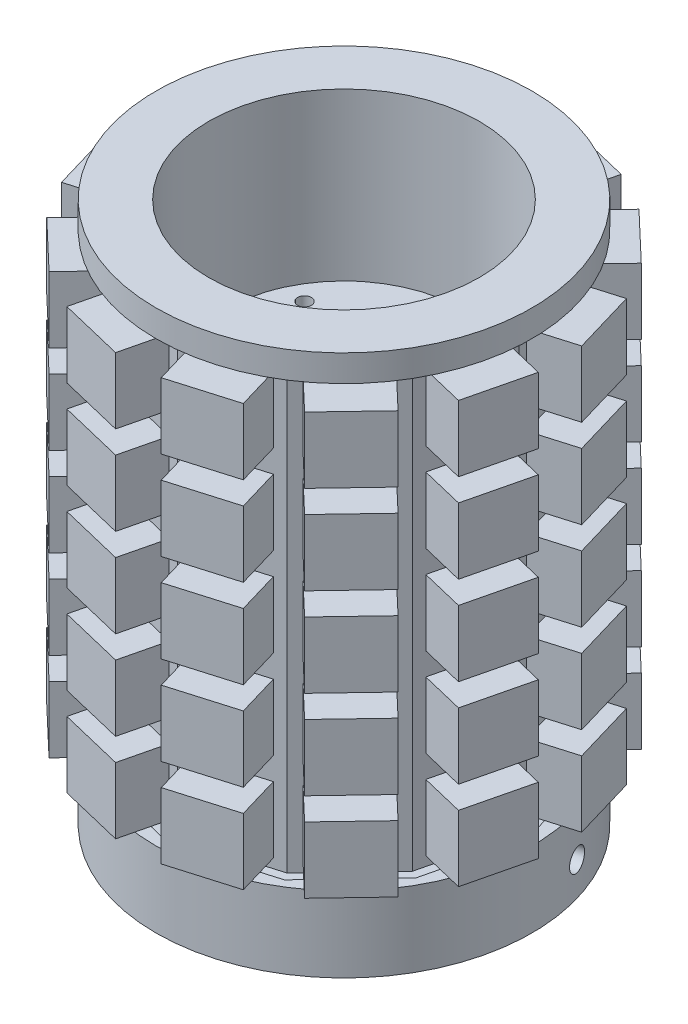
SolidWorks part; units mm, degrees
ref_plane "Front Plane" through (0, 0, 0) normal (0, 0, 1) x (1, 0, 0)
ref_plane "Top Plane" through (0, 0, 0) normal (0, 1, 0) x (1, 0, 0)
ref_plane "Right Plane" through (0, 0, 0) normal (1, 0, 0) x (0, 0, -1)
sketch "Sketch1" plane through (0, 0, 0) normal (0, 1, 0) x (1, 0, 0)
  circle A0 centre (0, 0) radius 36
ref_plane "Plane1" through (0, 70, 0) normal (0, 1, 0) x (1, 0, 0)
sketch "Sketch2" plane through (0, 70, 0) normal (0, 1, 0) x (1, 0, 0)
  circle A0 centre (0, 0) radius 27
loft "Loft1" add profiles "Sketch1", "Sketch2" connector at (17.6791, 0, 31.36) connector at (22.1968, 70, 15.3721)
sketch "Sketch3" plane through (0, 0, 0) normal (0, -1, 0) x (-1, 0, 0)
  line L1 (-17.8313, 32.7276) -> (-31.8061, 19.4273)
  line L2 (-31.8061, 19.4273) -> (-37.2586, 0.9214)
  line L3 (-37.2586, 0.9214) -> (-32.7276, -17.8313)
  line L4 (-32.7276, -17.8313) -> (-19.4273, -31.8061)
  line L5 (-19.4273, -31.8061) -> (-0.9214, -37.2586)
  line L6 (-0.9214, -37.2586) -> (17.8313, -32.7276)
  line L7 (17.8313, -32.7276) -> (31.8061, -19.4273)
  line L8 (31.8061, -19.4273) -> (37.2586, -0.9214)
  line L9 (37.2586, -0.9214) -> (32.7276, 17.8313)
  line L10 (32.7276, 17.8313) -> (19.4273, 31.8061)
  line L11 (19.4273, 31.8061) -> (0.9214, 37.2586)
  line L12 (0.9214, 37.2586) -> (-17.8313, 32.7276)
  circle A0 centre (0, 0) radius 36 construction
  circle A1 centre (0, 0) radius 36 construction
extrude "Extrude-Thin2" add sketch "Sketch3" against normal blind 100 separate body thin thin type one direction wall 1.2
ref_axis "Axis1" through (0, 0, 0) along (0, 1, 0)
sketch "Sketch4" plane through (-10.5135, 0, -35.6834) normal (-0.2826, 0, -0.9592) x (-0.9592, 0, 0.2826)
  line L0 (9.9677, 100) -> (-9.9677, 100) construction
  line L1 (-7.45, 97) -> (7.45, 97)
  line L2 (-7.45, 97) -> (-7.45, 82.1)
  line L3 (-7.45, 82.1) -> (7.45, 82.1)
  line L4 (7.45, 97) -> (7.45, 82.1)
  line L5 (-7.45, 97) -> (7.45, 82.1) construction
  line L6 (-7.45, 82.1) -> (7.45, 97) construction
  point P0 (0, 89.55)
  dimension "D1" = 14.9
  dimension "D2" = 14.9
  dimension "D3" = 3
extrude "Boss-Extrude1" add sketch "Sketch4" along normal blind 10
pattern_circular "CirPattern1" count 12 over 360 about axis through (0, 0, 0) along (0, 1, 0) of "Boss-Extrude1"
pattern_linear "LPattern1" count 5 spacing 20 along (0, -1, 0) of "CirPattern1"
sketch "Sketch5" plane through (0, 100, 0) normal (0, 1, 0) x (1, 0, 0)
  line L1 (0.9214, -37.2586) -> (19.4273, -31.8061)
  line L2 (19.4273, -31.8061) -> (32.7276, -17.8313)
  line L3 (32.7276, -17.8313) -> (37.2586, 0.9214)
  line L4 (37.2586, 0.9214) -> (31.8061, 19.4273)
  line L5 (31.8061, 19.4273) -> (17.8313, 32.7276)
  line L6 (17.8313, 32.7276) -> (-0.9214, 37.2586)
  line L7 (-0.9214, 37.2586) -> (-19.4273, 31.8061)
  line L8 (-19.4273, 31.8061) -> (-32.7276, 17.8313)
  line L9 (-32.7276, 17.8313) -> (-37.2586, -0.9214)
  line L10 (-37.2586, -0.9214) -> (-31.8061, -19.4273)
  line L11 (-31.8061, -19.4273) -> (-17.8313, -32.7276)
  line L12 (-17.8313, -32.7276) -> (0.9214, -37.2586)
  circle A0 centre (0, 0) radius 36 construction
  dimension "D1" = 32.7276
  dimension "D2" = 37.2586
  dimension "D3" = 17.8313
sketch "Sketch6" plane through (0, 0, 0) normal (0, -1, 0) x (1, 0, 0)
  line L36 (-40.4255, 0.9998) -> (-35.5094, -19.3469)
  line L37 (-34.5097, 21.0786) -> (-40.4255, 0.9998)
  line L38 (-35.5094, -19.3469) -> (-21.0786, -34.5097)
  line L39 (-21.0786, -34.5097) -> (-0.9998, -40.4255)
  line L40 (-0.9998, -40.4255) -> (19.3469, -35.5094)
  line L41 (19.3469, -35.5094) -> (34.5097, -21.0786)
  line L42 (34.5097, -21.0786) -> (40.4255, -0.9998)
  line L43 (40.4255, -0.9998) -> (35.5094, 19.3469)
  line L44 (35.5094, 19.3469) -> (21.0786, 34.5097)
  line L45 (21.0786, 34.5097) -> (0.9998, 40.4255)
  line L46 (0.9998, 40.4255) -> (-19.3469, 35.5094)
  line L47 (-19.3469, 35.5094) -> (-34.5097, 21.0786)
  circle A0 centre (0, 0) radius 42.3635
  dimension "D1" = 84.727
extrude "Boss-Extrude2" add sketch "Sketch6" along normal blind 12 separate body
sketch "Sketch7" plane through (0, -12, 0) normal (0, -1, 0) x (-1, 0, 0)
  circle A0 centre (0, 0) radius 42.3635 construction
  circle A1 centre (0, 0) radius 42.3635
extrude "Boss-Extrude3" add sketch "Sketch7" along normal blind 5
ref_plane "Plane2" through (0, 0, 0) normal (0.9592, 0, -0.2826) x (-0.2826, 0, -0.9592)
ref_plane "Plane3" [suppressed] through (0, 0, 0) normal (-0.2826, 0, -0.9592) x (-0.9592, 0, 0.2826)
sketch "Sketch8" plane through (37.4676, 0, -11.0392) normal (-0.9592, 0, 0.2826) x (0.2826, 0, 0.9592)
  line L0 (-42.3635, -17) -> (42.3635, -17) construction
  circle A0 centre (0, -9.5) radius 2.5
  dimension "D1" = 7.5
extrude "Cut-Extrude1" cut sketch "Sketch8" against normal blind 10
sketch "Sketch10" plane through (0, 100, 0) normal (0, 1, 0) x (1, 0, 0)
  line L13 (-35.5094, 19.3469) -> (-40.4255, -0.9998)
  line L14 (-40.4255, -0.9998) -> (-34.5097, -21.0786)
  line L15 (-34.5097, -21.0786) -> (-19.3469, -35.5094)
  line L16 (-19.3469, -35.5094) -> (0.9998, -40.4255)
  line L17 (0.9998, -40.4255) -> (21.0786, -34.5097)
  line L18 (21.0786, -34.5097) -> (35.5094, -19.3469)
  line L19 (35.5094, -19.3469) -> (40.4255, 0.9998)
  line L20 (40.4255, 0.9998) -> (37.4676, 11.0392)
  line L21 (37.4676, 11.0392) -> (34.5097, 21.0786)
  line L22 (34.5097, 21.0786) -> (19.3469, 35.5094)
  line L23 (19.3469, 35.5094) -> (-0.9998, 40.4255)
  line L24 (-0.9998, 40.4255) -> (-21.0786, 34.5097)
  line L25 (-21.0786, 34.5097) -> (-35.5094, 19.3469)
  line L26 (-35.5094, 19.3469) -> (-40.4255, -0.9998)
  line L27 (-40.4255, -0.9998) -> (-34.5097, -21.0786)
  line L28 (-34.5097, -21.0786) -> (-19.3469, -35.5094)
  line L29 (-19.3469, -35.5094) -> (0.9998, -40.4255)
  line L30 (0.9998, -40.4255) -> (21.0786, -34.5097)
  line L31 (21.0786, -34.5097) -> (35.5094, -19.3469)
  line L32 (35.5094, -19.3469) -> (40.4255, 0.9998)
  line L33 (40.4255, 0.9998) -> (37.4676, 11.0392)
  line L35 (34.5097, 21.0786) -> (19.3469, 35.5094)
  line L36 (19.3469, 35.5094) -> (-0.9998, 40.4255)
  line L37 (-0.9998, 40.4255) -> (-21.0786, 34.5097)
  line L38 (-21.0786, 34.5097) -> (-35.5094, 19.3469)
  line L39 (37.4676, 11.0392) -> (34.5097, 21.0786)
  circle A1 centre (0, 0) radius 42.3635
  circle A2 centre (0, 0) radius 42.3635
  dimension "D1" = 0
  dimension "D2" = 0
extrude "Boss-Extrude4" add sketch "Sketch10" against normal blind 1 and the other way blind 3 separate body
sketch "Sketch11" plane through (0, 103, 0) normal (0, 1, 0) x (1, 0, 0)
  circle A0 centre (0, 0) radius 42.3635 construction
  circle A1 centre (0, 0) radius 42.3635
extrude "Boss-Extrude5" add sketch "Sketch11" along normal blind 2
sketch "Sketch12" plane through (0, 105, 0) normal (0, 1, 0) x (1, 0, 0)
  circle A1 centre (0, 0) radius 32.5
  circle A2 centre (0, 0) radius 30.5
  dimension "D1" = 2
  dimension "D2" = 65
extrude "Boss-Extrude6" add sketch "Sketch12" against normal blind 95
sketch "Sketch13" plane through (0, 105, 0) normal (0, 1, 0) x (1, 0, 0)
  circle A0 centre (0, 0) radius 30.5 construction
  circle A1 centre (0, 0) radius 30.5
extrude "Cut-Extrude3" cut sketch "Sketch13" against normal blind 95
sketch "Sketch14" plane through (0, 10, 0) normal (0, -1, 0) x (1, 0, 0)
  circle A0 centre (0, 0) radius 32.5
extrude "Boss-Extrude7" add sketch "Sketch14" along normal blind 2
sketch "Sketch9" plane through (0, -17, 0) normal (0, -1, 0) x (-1, 0, 0)
  line L0 (9.3692, 31.7997) -> (-9.3692, -31.7997) construction
  line L1 (0.9214, 37.2586) -> (19.4273, 31.8061) construction
  circle A0 centre (-10.6566, 19.5592) radius 1.55
  circle A1 centre (-20.5625, -14.0619) radius 1.55
  circle A2 centre (9.6533, -22.9645) radius 1.55
  circle A3 centre (19.5592, 10.6566) radius 1.55
  point P8 (0, 0)
  dimension "D1" = 15.75
  dimension "D2" = 15.75
  dimension "D3" = 35.05
  dimension "D4" = 20.25
extrude "Cut-Extrude2" cut sketch "Sketch9" against normal blind 138
sketch "Sketch15" plane through (0, -17, 0) normal (0, -1, 0) x (1, 0, 0)
  line L0 (-9.3692, -31.7997) -> (9.3692, 31.7997) construction
  circle A0 centre (-9.6533, 22.9645) radius 2.85
  circle A1 centre (-19.5592, -10.6566) radius 2.85
  circle A2 centre (10.6566, -19.5592) radius 2.85
  circle A3 centre (20.5625, 14.0619) radius 2.85
extrude "Cut-Extrude4" cut sketch "Sketch15" against normal blind 3.2
